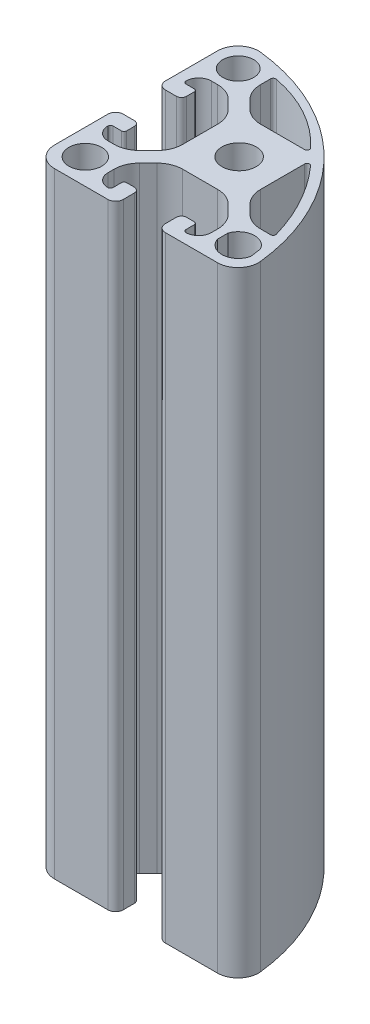
SolidWorks part; units mm, degrees
ref_plane "Alzado" through (0, 0, 0) normal (0, 0, 1) x (1, 0, 0)
ref_plane "Planta" through (0, 0, 0) normal (0, 1, 0) x (1, 0, 0)
ref_plane "Vista lateral" through (0, 0, 0) normal (1, 0, 0) x (0, 0, -1)
sketch "Croquis1" plane through (0, 0, 0) normal (0, 1, 0) x (1, 0, 0)
  line L0 (-18.2, 12.3) -> (-18.2, 15.7771)
  line L1 (-12.3, 11.8) -> (-17.7, 11.8)
  line L2 (-11.8, 16.9053) -> (-11.8, 12.3)
  line L3 (11.8, -17.7) -> (11.8, -12.3)
  line L4 (15.7771, -18.2) -> (12.3, -18.2)
  line L5 (12.3, -11.8) -> (16.9053, -11.8)
  line L6 (-18.2, -16) -> (-18.2, -12.3)
  line L7 (-12.3, -18.2) -> (-16, -18.2)
  line L8 (-11.8, -12.3) -> (-11.8, -17.7)
  line L9 (-17.7, -11.8) -> (-12.3, -11.8)
  line L10 (-10.1, 14.2924) -> (-10.1, 16.2371)
  line L11 (-6.9431, 9.0645) -> (-8.6355, 10.7569)
  line L12 (5.1332, 7.6) -> (-3.4076, 7.6)
  line L13 (4.1, -16.35) -> (4.1, -18.5)
  line L14 (5.6, -20) -> (15.7771, -20)
  line L15 (-20, 15.7771) -> (-20, 5.6)
  line L16 (-18.5, 4.1) -> (-16.35, 4.1)
  line L17 (-15.35, 5.1) -> (-15.35, 6.6)
  line L18 (-15.85, 7.1) -> (-17.5, 7.1)
  line L19 (-15.5, 10.1) -> (-14.2924, 10.1)
  line L20 (-10.7569, 8.6355) -> (-9.0645, 6.9431)
  line L21 (-7.6, 3.4076) -> (-7.6, -3.4076)
  line L22 (-9.0645, -6.9431) -> (-10.7569, -8.6355)
  line L23 (-14.2924, -10.1) -> (-15.5, -10.1)
  line L24 (-17.5, -7.1) -> (-15.85, -7.1)
  line L25 (-15.35, -6.6) -> (-15.35, -5.1)
  line L26 (-16.35, -4.1) -> (-18.5, -4.1)
  line L27 (-20, -5.6) -> (-20, -16)
  line L28 (-16, -20) -> (-5.6, -20)
  line L29 (-4.1, -18.5) -> (-4.1, -16.35)
  line L30 (-5.1, -15.35) -> (-6.6, -15.35)
  line L31 (-7.1, -15.85) -> (-7.1, -17.5)
  line L32 (-10.1, -15.5) -> (-10.1, -14.2924)
  line L33 (-8.6355, -10.7569) -> (-6.9431, -9.0645)
  line L34 (-3.4076, -7.6) -> (3.4076, -7.6)
  line L35 (6.9431, -9.0645) -> (8.6355, -10.7569)
  line L36 (10.1, -14.2924) -> (10.1, -15.5)
  line L37 (7.1, -17.5) -> (7.1, -15.85)
  line L38 (6.6, -15.35) -> (5.1, -15.35)
  line L39 (16.2371, -10.1) -> (14.2924, -10.1)
  line L40 (10.7569, -8.6355) -> (9.0645, -6.9431)
  line L41 (7.6, -3.4076) -> (7.6, 5.1332)
  circle A0 centre (0, 0) radius 3.35
  arc A1 (-15.7556, 17.9635) -> (-18.2, 15.7771) centre (-16, 15.7771) ccw
  arc A2 (-18.2, 12.3) -> (-17.7, 11.8) centre (-17.7, 12.3) ccw
  arc A3 (-12.3, 11.8) -> (-11.8, 12.3) centre (-12.3, 12.3) ccw
  arc A4 (-11.8, 16.9053) -> (-12.1979, 17.3947) centre (-12.3, 16.9053) ccw
  arc A5 (-12.1979, 17.3947) -> (-15.7556, 17.9635) centre (-20, -20) ccw
  arc A6 (12.3, -11.8) -> (11.8, -12.3) centre (12.3, -12.3) ccw
  arc A7 (11.8, -17.7) -> (12.3, -18.2) centre (12.3, -17.7) ccw
  arc A8 (15.7771, -18.2) -> (17.9635, -15.7556) centre (15.7771, -16) ccw
  arc A9 (17.9635, -15.7556) -> (17.3947, -12.1979) centre (-20, -20) ccw
  arc A10 (17.3947, -12.1979) -> (16.9053, -11.8) centre (16.9053, -12.3) ccw
  arc A11 (-17.7, -11.8) -> (-18.2, -12.3) centre (-17.7, -12.3) ccw
  arc A12 (-18.2, -16) -> (-16, -18.2) centre (-16, -16) ccw
  arc A13 (-12.3, -18.2) -> (-11.8, -17.7) centre (-12.3, -17.7) ccw
  arc A14 (-11.8, -12.3) -> (-12.3, -11.8) centre (-12.3, -12.3) ccw
  arc A15 (4.1, -18.5) -> (5.6, -20) centre (5.6, -18.5) ccw
  arc A16 (15.7771, -20) -> (19.7523, -15.5556) centre (15.7771, -16) ccw
  arc A17 (19.7523, -15.5556) -> (-15.5556, 19.7523) centre (-20, -20) ccw
  arc A18 (-15.5556, 19.7523) -> (-20, 15.7771) centre (-16, 15.7771) ccw
  arc A19 (-20, 5.6) -> (-18.5, 4.1) centre (-18.5, 5.6) ccw
  arc A20 (-16.35, 4.1) -> (-15.35, 5.1) centre (-16.35, 5.1) ccw
  arc A21 (-15.35, 6.6) -> (-15.85, 7.1) centre (-15.85, 6.6) ccw
  arc A22 (-18, 7.6) -> (-17.5, 7.1) centre (-17.5, 7.6) ccw
  arc A23 (-15.5, 10.1) -> (-18, 7.6) centre (-15.5, 7.6) ccw
  arc A24 (-10.7569, 8.6355) -> (-14.2924, 10.1) centre (-14.2924, 5.1) ccw
  arc A25 (-7.6, 3.4076) -> (-9.0645, 6.9431) centre (-12.6, 3.4076) ccw
  arc A26 (-9.0645, -6.9431) -> (-7.6, -3.4076) centre (-12.6, -3.4076) ccw
  arc A27 (-14.2924, -10.1) -> (-10.7569, -8.6355) centre (-14.2924, -5.1) ccw
  arc A28 (-18, -7.6) -> (-15.5, -10.1) centre (-15.5, -7.6) ccw
  arc A29 (-17.5, -7.1) -> (-18, -7.6) centre (-17.5, -7.6) ccw
  arc A30 (-15.85, -7.1) -> (-15.35, -6.6) centre (-15.85, -6.6) ccw
  arc A31 (-15.35, -5.1) -> (-16.35, -4.1) centre (-16.35, -5.1) ccw
  arc A32 (-18.5, -4.1) -> (-20, -5.6) centre (-18.5, -5.6) ccw
  arc A33 (-20, -16) -> (-16, -20) centre (-16, -16) ccw
  arc A34 (-5.6, -20) -> (-4.1, -18.5) centre (-5.6, -18.5) ccw
  arc A35 (-4.1, -16.35) -> (-5.1, -15.35) centre (-5.1, -16.35) ccw
  arc A36 (-6.6, -15.35) -> (-7.1, -15.85) centre (-6.6, -15.85) ccw
  arc A37 (-7.6, -18) -> (-7.1, -17.5) centre (-7.6, -17.5) ccw
  arc A38 (-10.1, -15.5) -> (-7.6, -18) centre (-7.6, -15.5) ccw
  arc A39 (-8.6355, -10.7569) -> (-10.1, -14.2924) centre (-5.1, -14.2924) ccw
  arc A40 (-3.4076, -7.6) -> (-6.9431, -9.0645) centre (-3.4076, -12.6) ccw
  arc A41 (6.9431, -9.0645) -> (3.4076, -7.6) centre (3.4076, -12.6) ccw
  arc A42 (10.1, -14.2924) -> (8.6355, -10.7569) centre (5.1, -14.2924) ccw
  arc A43 (7.6, -18) -> (10.1, -15.5) centre (7.6, -15.5) ccw
  arc A44 (7.1, -17.5) -> (7.6, -18) centre (7.6, -17.5) ccw
  arc A45 (7.1, -15.85) -> (6.6, -15.35) centre (6.6, -15.85) ccw
  arc A46 (5.1, -15.35) -> (4.1, -16.35) centre (5.1, -16.35) ccw
  arc A47 (-9.4621, 16.7177) -> (-10.1, 16.2371) centre (-9.6, 16.2371) ccw
  arc A48 (-10.1, 14.2924) -> (-8.6355, 10.7569) centre (-5.1, 14.2924) ccw
  arc A49 (-6.9431, 9.0645) -> (-3.4076, 7.6) centre (-3.4076, 12.6) ccw
  arc A50 (5.1332, 7.6) -> (5.4666, 8.4727) centre (5.1332, 8.1) ccw
  arc A51 (16.7177, -9.4621) -> (8.4727, 5.4666) centre (-20, -20) ccw
  arc A52 (16.2371, -10.1) -> (16.7177, -9.4621) centre (16.2371, -9.6) ccw
  arc A53 (10.7569, -8.6355) -> (14.2924, -10.1) centre (14.2924, -5.1) ccw
  arc A54 (7.6, -3.4076) -> (9.0645, -6.9431) centre (12.6, -3.4076) ccw
  arc A55 (8.4727, 5.4666) -> (7.6, 5.1332) centre (8.1, 5.1332) ccw
  arc A56 (-9.4621, 16.7177) -> (5.4666, 8.4727) centre (-14.5044, -10.0495) cw
extrude "Saliente-Extruir1" add sketch "Croquis1" along normal blind 120
sketch "Croquis2" plane through (0, 120, 0) normal (0, 1, 0) x (1, 0, 0)
  line L0 (-18.2, 15.7771) -> (-18.2, 12.3) construction
  line L1 (-17.7, 11.8) -> (-12.3, 11.8) construction
  line L2 (-11.8, 12.3) -> (-11.8, 16.9053) construction
  line L3 (-18.2, 15.7771) -> (-18.2, 12.3)
  line L4 (-17.7, 11.8) -> (-12.3, 11.8)
  line L5 (-11.8, 12.3) -> (-11.8, 16.9053)
  line L6 (-16, -18.2) -> (-12.3, -18.2) construction
  line L7 (-18.2, -12.3) -> (-18.2, -16) construction
  line L8 (-12.3, -11.8) -> (-17.7, -11.8) construction
  line L9 (-11.8, -17.7) -> (-11.8, -12.3) construction
  line L10 (-16, -18.2) -> (-12.3, -18.2)
  line L11 (-18.2, -12.3) -> (-18.2, -16)
  line L12 (-12.3, -11.8) -> (-17.7, -11.8)
  line L13 (-11.8, -17.7) -> (-11.8, -12.3)
  line L14 (12.3, -18.2) -> (15.7771, -18.2) construction
  line L15 (11.8, -12.3) -> (11.8, -17.7) construction
  line L16 (16.9053, -11.8) -> (12.3, -11.8) construction
  line L17 (12.3, -18.2) -> (15.7771, -18.2)
  line L18 (11.8, -12.3) -> (11.8, -13.9666)
  line L19 (16.9053, -11.8) -> (12.3, -11.8)
  line L20 (11.8, -16.0334) -> (11.8, -17.7)
  arc A0 (-11.8, 16.9053) -> (-12.1979, 17.3947) centre (-12.3, 16.9053) ccw construction
  arc A1 (-12.1979, 17.3947) -> (-15.7556, 17.9635) centre (-20, -20) ccw construction
  arc A2 (-15.7556, 17.9635) -> (-18.2, 15.7771) centre (-16, 15.7771) ccw construction
  arc A3 (-18.2, 12.3) -> (-17.7, 11.8) centre (-17.7, 12.3) ccw construction
  arc A4 (-12.3, 11.8) -> (-11.8, 12.3) centre (-12.3, 12.3) ccw construction
  arc A5 (-11.8, 16.9053) -> (-12.1979, 17.3947) centre (-12.3, 16.9053) ccw
  arc A6 (-12.1979, 17.3947) -> (-15.7556, 17.9635) centre (-20, -20) ccw
  arc A7 (-15.7556, 17.9635) -> (-18.2, 15.7771) centre (-16, 15.7771) ccw
  arc A8 (-18.2, 12.3) -> (-17.7, 11.8) centre (-17.7, 12.3) ccw
  arc A9 (-12.3, 11.8) -> (-11.8, 12.3) centre (-12.3, 12.3) ccw
  arc A10 (-12.3, -18.2) -> (-11.8, -17.7) centre (-12.3, -17.7) ccw construction
  arc A11 (-18.2, -16) -> (-16, -18.2) centre (-16, -16) ccw construction
  arc A12 (-17.7, -11.8) -> (-18.2, -12.3) centre (-17.7, -12.3) ccw construction
  arc A13 (-11.8, -12.3) -> (-12.3, -11.8) centre (-12.3, -12.3) ccw construction
  arc A14 (-12.3, -18.2) -> (-11.8, -17.7) centre (-12.3, -17.7) ccw
  arc A15 (-18.2, -16) -> (-16, -18.2) centre (-16, -16) ccw
  arc A16 (-17.7, -11.8) -> (-18.2, -12.3) centre (-17.7, -12.3) ccw
  arc A17 (-11.8, -12.3) -> (-12.3, -11.8) centre (-12.3, -12.3) ccw
  arc A18 (17.3947, -12.1979) -> (16.9053, -11.8) centre (16.9053, -12.3) ccw construction
  arc A19 (17.9635, -15.7556) -> (17.3947, -12.1979) centre (-20, -20) ccw construction
  arc A20 (15.7771, -18.2) -> (17.9635, -15.7556) centre (15.7771, -16) ccw construction
  arc A21 (11.8, -17.7) -> (12.3, -18.2) centre (12.3, -17.7) ccw construction
  arc A22 (12.3, -11.8) -> (11.8, -12.3) centre (12.3, -12.3) ccw construction
  arc A23 (17.3947, -12.1979) -> (16.9053, -11.8) centre (16.9053, -12.3) ccw
  arc A24 (17.9635, -15.7556) -> (17.9551, -15.6816) centre (-20, -20) ccw
  arc A25 (15.7771, -18.2) -> (17.9635, -15.7556) centre (15.7771, -16) ccw
  arc A26 (11.8, -17.7) -> (12.3, -18.2) centre (12.3, -17.7) ccw
  arc A27 (12.3, -11.8) -> (11.8, -12.3) centre (12.3, -12.3) ccw
  circle A28 centre (-14.9928, 14.8209) radius 3.0209
  circle A29 centre (-15, -15) radius 3.2
  circle A30 centre (14.8285, -15) radius 3.2
  arc A31 (17.6371, -13.4664) -> (17.3947, -12.1979) centre (-20, -20) ccw
extrude "Saliente-Extruir2" add sketch "Croquis2" against normal up to surface (120 mm away) contours A29 L13 A17 L12 | A29 L10 A14 L13 | A29 L11 A15 L10 | A29 L12 A16 L11 | A28 A6 A7 L3 A8 L4 | A28 L4 A9 L5 A5 A6 | A30 A31 A23 L19 | A30 L19 A27 L18 | A30 L20 A26 L17 | A30 L17 A25 A24 region at (-17.4189, 120, -17.3634) region at (-13.3889, 120, -17.5545) region at (-17.285, 120, 17.285) region at (-12.5299, 120, 17.4701) region at (-17.4701, 120, 12.5299) region at (-12.5299, 120, 12.5299) region at (12.5158, 120, 17.6045) region at (17.0357, 120, 17.362) region at (12.5158, 120, 12.3955) region at (16.8311, 120, 12.2576) up to face at (-4.7129, 0, -11.4358)
